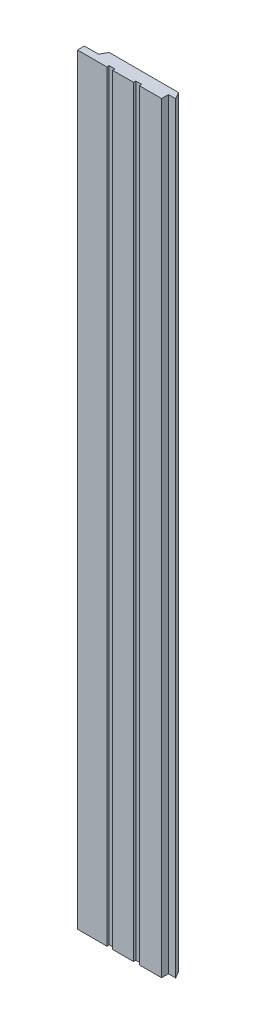
SolidWorks part; units mm, degrees
ref_plane "Front Plane" through (0, 0, 0) normal (0, 0, 1) x (1, 0, 0)
ref_plane "Top Plane" through (0, 0, 0) normal (0, 1, 0) x (1, 0, 0)
ref_plane "Right Plane" through (0, 0, 0) normal (1, 0, 0) x (0, 0, -1)
sketch "Sketch1" plane through (0, 0, 0) normal (0, 1, 0) x (1, 0, 0)
  line L0 (-60, 0) -> (-41.5, 0)
  line L1 (-60, 9) -> (60, 9)
  line L2 (-60, 9) -> (-60, -9)
  line L3 (-60, -9) -> (60, -9)
  line L4 (60, 9) -> (60, -9)
  line L5 (-60, 9) -> (60, -9) construction
  line L6 (-60, -9) -> (60, 9) construction
  line L7 (-41.5, 0) -> (-36.3038, 9)
  line L8 (-41.5, 0) -> (-41.5, 9) construction
  line L9 (60, 0) -> (54.8038, 9)
  line L10 (60, 0) -> (50.5, 0)
  line L11 (50.5, 0) -> (50.5, -9)
  line L12 (-17.5, 9) -> (-17.5, -9) construction
  line L13 (0, 9) -> (0, -9) construction
  line L14 (-21.25, -6) -> (-13.75, -6)
  line L15 (-21.25, -6) -> (-21.25, -9)
  line L16 (-21.25, -9) -> (-13.75, -9)
  line L17 (-13.75, -6) -> (-13.75, -9)
  line L18 (-21.25, -6) -> (-13.75, -9) construction
  line L19 (-21.25, -9) -> (-13.75, -6) construction
  line L20 (13.75, -6) -> (13.75, -9)
  line L21 (21.25, -6) -> (13.75, -6)
  line L22 (21.25, -6) -> (21.25, -9)
  point P0 (0, 0)
  point P16 (-17.5, -7.5)
  dimension "D1" = 120
  dimension "D2" = 18
  dimension "D3" = 18.5
  dimension "D4" = 30
  dimension "D5" = 9.5
  dimension "D6" = 30
  dimension "D7" = 7.5
  dimension "D8" = 3
  dimension "D9" = 17.5
extrude "Shape" add sketch "Sketch1" along normal blind 1000 contours L21 L22 L3 L11 L10 L9 L1 L7 L0 L2 L15 L14 L17 L20 region at (1.8133, 0, 0.1694)
equation "\"D9@Sketch1\"=35/2"
